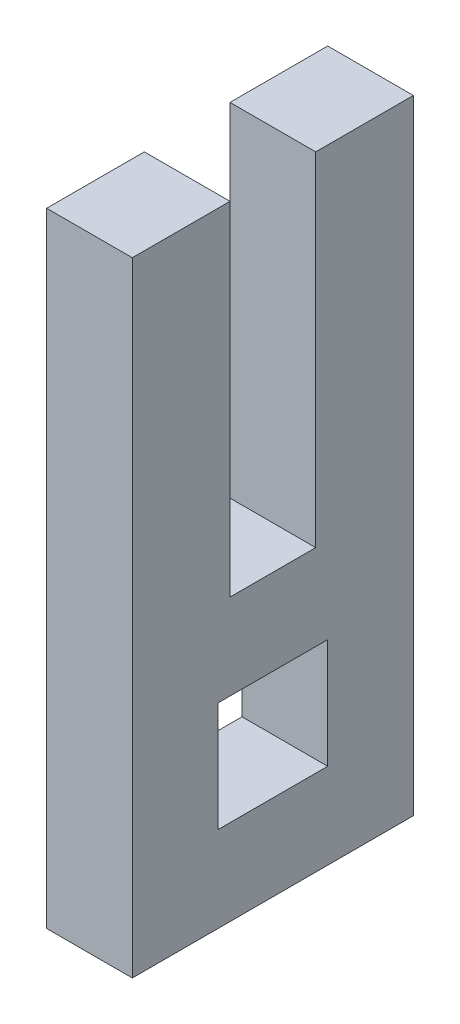
SolidWorks part; units mm, degrees
material "Balsa"
ref_plane "Front Plane" through (0, 0, 0) normal (0, 0, 1) x (1, 0, 0)
ref_plane "Top Plane" through (0, 0, 0) normal (0, 1, 0) x (1, 0, 0)
ref_plane "Right Plane" through (0, 0, 0) normal (1, 0, 0) x (0, 0, -1)
sketch "Sketch2" plane through (0, 0, 0) normal (1, 0, 0) x (0, 0, -1)
  line L0 (0, 0) -> (0, 46.228)
  line L1 (0, 46.228) -> (7.239, 46.228)
  line L2 (7.239, 46.228) -> (7.239, 20.828)
  line L3 (7.239, 20.828) -> (13.589, 20.828)
  line L4 (13.589, 20.828) -> (13.589, 46.228)
  line L5 (13.589, 46.228) -> (20.828, 46.228)
  line L6 (20.828, 46.228) -> (20.828, 0)
  line L7 (20.828, 0) -> (0, 0)
  line L9 (6.35, 6.35) -> (14.478, 6.35)
  line L10 (6.35, 6.35) -> (6.35, 14.478)
  line L11 (6.35, 14.478) -> (14.478, 14.478)
  line L12 (14.478, 6.35) -> (14.478, 14.478)
  point P13 (10.414, 20.828)
  point P16 (10.414, 0)
  dimension "D1" = 6.35
  dimension "D2" = 8.128
  dimension "D3" = 8.128
  dimension "D4" = 6.35
  dimension "D5" = 6.35
  dimension "D6" = 6.35
  dimension "D7" = 6.35
  dimension "D8" = 25.4
extrude "Boss-Extrude1" add sketch "Sketch2" along normal blind 6.35
equation "\"D4@Sketch2\"=\"D5@Sketch2\""
equation "\"D6@Sketch2\"=\"D5@Sketch2\""
